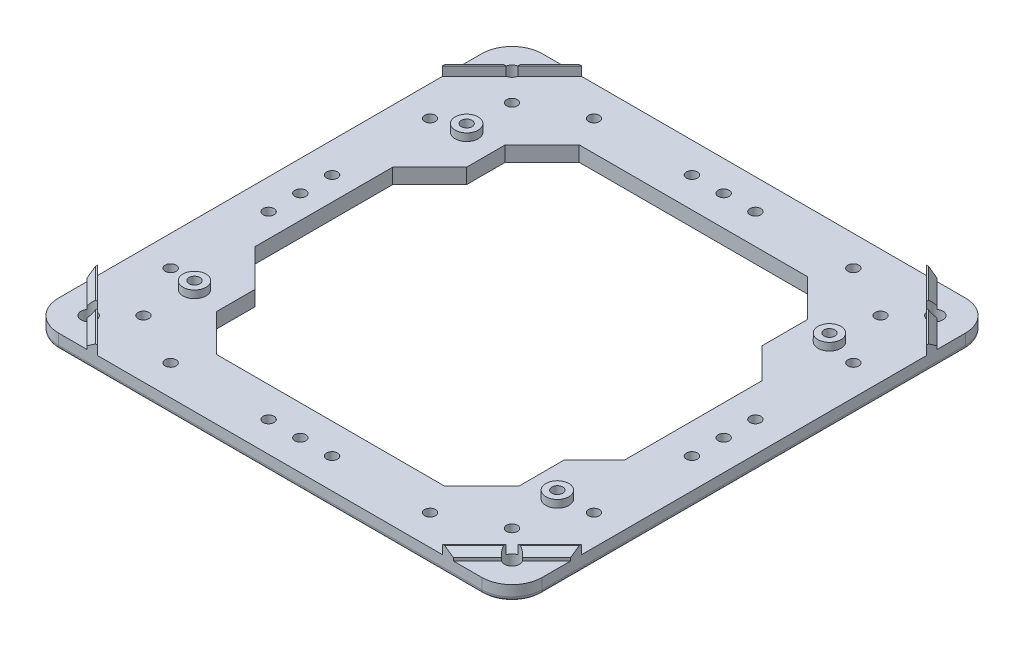
SolidWorks part; units mm, degrees
ref_plane "Front Plane" through (0, 0, 0) normal (0, 0, 1) x (1, 0, 0)
ref_plane "Top Plane" through (0, 0, 0) normal (0, 1, 0) x (1, 0, 0)
ref_plane "Right Plane" through (0, 0, 0) normal (1, 0, 0) x (0, 0, -1)
sketch "Sketch1" plane through (0, 0, 0) normal (0, 1, 0) x (1, 0, 0)
  line L1 (0, 0) -> (203.2, 0)
  line L2 (0, 0) -> (0, 203.2)
  line L3 (0, 203.2) -> (203.2, 203.2)
  line L4 (203.2, 0) -> (203.2, 203.2)
  dimension "D1" = 203.2
  dimension "D2" = 203.2
extrude "Boss-Extrude1" add sketch "Sketch1" along normal blind 6.35
fillet "Fillet1" radius 12.7 4 edges at (0, 3.175, -203.2) (0, 3.175, 0) (203.2, 3.175, 0) (203.2, 3.175, -203.2)
sketch "Sketch2" plane through (0, 0, 0) normal (0, -1, 0) x (1, 0, 0)
  circle A0 centre (12.7, -12.7) radius 3.175
  circle A1 centre (190.5, -12.7) radius 3.175
  circle A2 centre (190.5, -190.5) radius 3.175
  circle A3 centre (12.7, -190.5) radius 3.175
  arc A4 (190.5, -203.2) -> (203.2, -190.5) centre (190.5, -190.5) ccw construction
  arc A5 (12.7, 0) -> (0, -12.7) centre (12.7, -12.7) ccw construction
  arc A6 (12.7, 0) -> (0, -12.7) centre (12.7, -12.7) ccw construction
  dimension "D1" = 6.35
  dimension "D2" = 9.525
extrude "Cut-Extrude1" cut sketch "Sketch2" against normal through all
fillet "Fillet2" radius 1.905 8 edges at (3.7197, 0, -3.7197) (101.6, 0, 0) (199.4803, 0, -3.7197) (203.2, 0, -101.6) (199.4803, 0, -199.4803) (101.6, 0, -203.2) (3.7197, 0, -199.4803) (0, 0, -101.6)
sketch "Sketch3" plane through (0, 6.35, 0) normal (0, 1, 0) x (1, 0, 0)
  line L0 (3.7197, 3.7197) -> (24.1978, 24.1978) construction
  line L1 (24.1978, 24.1978) -> (0, 24.1978) construction
  line L2 (0, 190.5) -> (0, 12.7) construction
  line L3 (24.1978, 24.1978) -> (24.1978, 0) construction
  line L4 (12.7, 0) -> (190.5, 0) construction
  line L5 (3.7197, 199.4803) -> (24.1978, 179.0022) construction
  line L6 (0, 179.0022) -> (24.1978, 179.0022) construction
  line L7 (24.1978, 179.0022) -> (24.1978, 203.2) construction
  line L8 (190.5, 203.2) -> (12.7, 203.2) construction
  line L9 (199.4803, 3.7197) -> (179.0022, 24.1978) construction
  line L10 (179.0022, 24.1978) -> (179.0022, 0) construction
  line L12 (179.0022, 24.1978) -> (203.2, 24.1978) construction
  line L13 (203.2, 12.7) -> (203.2, 190.5) construction
  line L14 (199.4803, 199.4803) -> (179.0022, 179.0022) construction
  line L15 (179.0022, 179.0022) -> (203.2, 179.0022) construction
  line L16 (179.0022, 179.0022) -> (179.0022, 203.2) construction
  arc A0 (0, 12.7) -> (12.7, 0) centre (12.7, 12.7) ccw construction
  circle A1 centre (24.1978, 24.1978) radius 2.286
  arc A2 (190.5, 0) -> (203.2, 12.7) centre (190.5, 12.7) ccw construction
  arc A3 (203.2, 190.5) -> (190.5, 203.2) centre (190.5, 190.5) ccw construction
  arc A10 (12.7, 203.2) -> (0, 190.5) centre (12.7, 190.5) ccw construction
  circle A13 centre (179.0022, 179.0022) radius 2.286
  circle A14 centre (179.0022, 24.1978) radius 2.286
  circle A15 centre (24.1978, 179.0022) radius 2.286
  point P20 (101.6, 101.6)
  dimension "D2" = 4.572
  dimension "D1" = 28.9603
extrude "Cut-Extrude2" cut sketch "Sketch3" against normal through all
sketch "Sketch4" plane through (0, 6.35, 0) normal (0, 1, 0) x (1, 0, 0)
  line L0 (0, 190.5) -> (0, 12.7) construction
  line L1 (203.2, 12.7) -> (203.2, 190.5) construction
  line L2 (12.7, 0) -> (190.5, 0) construction
  line L3 (3.7197, 3.7197) -> (199.4803, 199.4803) construction
  circle A0 centre (47.117, 12.7) radius 2.286
  circle A1 centre (156.083, 12.7) radius 2.286
  arc A2 (0, 12.7) -> (12.7, 0) centre (12.7, 12.7) ccw construction
  arc A3 (203.2, 190.5) -> (190.5, 203.2) centre (190.5, 190.5) ccw construction
  circle A4 centre (12.7, 156.083) radius 2.286
  circle A5 centre (12.7, 47.117) radius 2.286
  circle A6 centre (156.083, 190.5) radius 2.286
  circle A7 centre (47.117, 190.5) radius 2.286
  circle A8 centre (190.5, 47.117) radius 2.286
  circle A9 centre (190.5, 156.083) radius 2.286
  circle A10 centre (101.6, 12.7) radius 2.286
  circle A11 centre (12.7, 101.6) radius 2.286
  circle A12 centre (101.6, 190.5) radius 2.286
  circle A13 centre (190.5, 101.6) radius 2.286
  point P18 (101.6, 101.6)
  dimension "D4" = 4.572
  dimension "D1" = 47.117
  dimension "D2" = 47.117
  dimension "D3" = 12.7
  dimension "D6" = 104.267
  dimension "D7" = 34.417
  dimension "D8" = 54.483
  dimension "D5" = 4
extrude "Cut-Extrude3" cut sketch "Sketch4" against normal through all
sketch "Sketch5" plane through (0, 6.35, 0) normal (0, 1, 0) x (1, 0, 0)
  line L0 (0, 190.5) -> (0, 12.7) construction
  line L1 (203.2, 12.7) -> (203.2, 190.5) construction
  line L2 (12.7, 0) -> (190.5, 0) construction
  line L3 (190.5, 203.2) -> (12.7, 203.2) construction
  circle A0 centre (25.4, 158.75) radius 2.286
  circle A1 centre (177.8, 158.75) radius 2.286
  circle A2 centre (177.8, 44.45) radius 2.286
  circle A3 centre (25.4, 44.45) radius 2.286
  circle A4 centre (25.4, 158.75) radius 4.826
  circle A5 centre (177.8, 158.75) radius 4.826
  circle A6 centre (177.8, 44.45) radius 4.826
  circle A7 centre (25.4, 44.45) radius 4.826
  dimension "D1" = 2.54
  dimension "D2" = 4.572
  dimension "D3" = 25.4
  dimension "D4" = 25.4
  dimension "D5" = 44.45
  dimension "D6" = 44.45
extrude "Boss-Extrude2" add sketch "Sketch5" along normal blind 3.175
sketch "Sketch6" plane through (0, 6.35, 0) normal (0, 1, 0) x (1, 0, 0)
  line L0 (203.2, 29.1287) -> (189.8864, 15.8151)
  line L1 (203.2, 12.7) -> (203.2, 190.5) construction
  line L2 (12.7, 0) -> (190.5, 0) construction
  line L3 (203.2, 29.1287) -> (203.2, 24.6386)
  line L4 (203.2, 24.6386) -> (193.0933, 14.5318)
  line L5 (178.5614, 0) -> (174.0713, 0)
  line L6 (187.3849, 13.3136) -> (174.0713, 0)
  line L7 (188.6682, 10.1067) -> (178.5614, 0)
  line L8 (3.7197, 3.7197) -> (199.4803, 199.4803) construction
  line L9 (13.3136, 15.8151) -> (0, 29.1287)
  line L10 (0, 24.6386) -> (0, 29.1287)
  line L11 (10.1067, 14.5318) -> (0, 24.6386)
  line L12 (24.6386, 0) -> (14.5318, 10.1067)
  line L13 (29.1287, 0) -> (15.8151, 13.3136)
  line L14 (29.1287, 0) -> (24.6386, 0)
  line L15 (15.8151, 189.8864) -> (29.1287, 203.2)
  line L16 (24.6386, 203.2) -> (29.1287, 203.2)
  line L17 (14.5318, 193.0933) -> (24.6386, 203.2)
  line L18 (0, 178.5614) -> (10.1067, 188.6682)
  line L19 (0, 174.0713) -> (13.3136, 187.3849)
  line L20 (0, 174.0713) -> (0, 178.5614)
  line L21 (189.8864, 187.3849) -> (203.2, 174.0713)
  line L22 (203.2, 178.5614) -> (203.2, 174.0713)
  line L23 (193.0933, 188.6682) -> (203.2, 178.5614)
  line L24 (178.5614, 203.2) -> (188.6682, 193.0933)
  line L25 (174.0713, 203.2) -> (187.3849, 189.8864)
  line L26 (174.0713, 203.2) -> (178.5614, 203.2)
  arc A0 (187.3849, 13.3136) -> (188.6682, 10.1067) centre (190.5, 12.7) ccw
  arc A1 (193.0933, 14.5318) -> (189.8864, 15.8151) centre (190.5, 12.7) ccw
  arc A2 (0, 12.7) -> (12.7, 0) centre (12.7, 12.7) ccw construction
  arc A3 (203.2, 190.5) -> (190.5, 203.2) centre (190.5, 190.5) ccw construction
  arc A4 (13.3136, 15.8151) -> (10.1067, 14.5318) centre (12.7, 12.7) ccw
  arc A5 (14.5318, 10.1067) -> (15.8151, 13.3136) centre (12.7, 12.7) ccw
  arc A6 (15.8151, 189.8864) -> (14.5318, 193.0933) centre (12.7, 190.5) ccw
  arc A7 (10.1067, 188.6682) -> (13.3136, 187.3849) centre (12.7, 190.5) ccw
  arc A8 (189.8864, 187.3849) -> (193.0933, 188.6682) centre (190.5, 190.5) ccw
  arc A9 (188.6682, 193.0933) -> (187.3849, 189.8864) centre (190.5, 190.5) ccw
  point P22 (101.6, 101.6)
  dimension "D4" = 6.35
  dimension "D1" = 29.1287
  dimension "D2" = 29.1287
  dimension "D3" = 3.175
  dimension "D6" = 177.8
  dimension "D5" = 4
extrude "Boss-Extrude3" add sketch "Sketch6" along normal blind 3.81
chamfer "Chamfer1" distance 2.54 angle 45 8 edges at (198.1466, 10.16, -19.5852) (183.6148, 10.16, -5.0534) (198.1466, 10.16, -183.6148) (183.6148, 10.16, -198.1466) (19.5852, 10.16, -198.1466) (5.0534, 10.16, -183.6148) (19.5852, 10.16, -5.0534) (5.0534, 10.16, -19.5852)
sketch "Sketch7" plane through (0, 6.35, 0) normal (0, 1, 0) x (1, 0, 0)
  line L0 (38.1, 57.15) -> (38.1, 25.4)
  line L1 (38.1, 177.8) -> (165.1, 177.8)
  line L2 (38.1, 177.8) -> (38.1, 146.05)
  line L3 (38.1, 25.4) -> (165.1, 25.4)
  line L4 (165.1, 177.8) -> (165.1, 146.05)
  line L5 (38.1, 57.15) -> (22.5685, 57.15)
  line L7 (38.1, 146.05) -> (22.5685, 146.05)
  line L8 (22.5685, 57.15) -> (22.5685, 146.05)
  line L9 (165.1, 57.15) -> (177.8, 57.15)
  line L11 (165.1, 146.05) -> (177.8, 146.05)
  line L12 (177.8, 57.15) -> (177.8, 146.05)
  line L13 (165.1, 57.15) -> (165.1, 25.4)
  circle A0 centre (47.117, 190.5) radius 2.286 construction
  circle A1 centre (101.6, 12.7) radius 2.286 construction
  circle A2 centre (177.8, 44.45) radius 4.826 construction
  circle A3 centre (25.4, 44.45) radius 2.286 construction
  circle A4 centre (190.5, 156.083) radius 2.286 construction
  circle A5 centre (177.8, 158.75) radius 4.826 construction
  circle A6 centre (25.4, 44.45) radius 4.826 construction
  dimension "D6" = 12.7
  dimension "D8" = 12.7
  dimension "D1" = 12.7
  dimension "D2" = 12.7
  dimension "D3" = 12.7
  dimension "D4" = 12.7
  dimension "D5" = 12.7
  dimension "D7" = 12.7
extrude "Cut-Extrude4" cut sketch "Sketch7" against normal through all
chamfer "Chamfer2" distance 15.5448 angle 45 8 edges at (22.5685, 3.175, -57.15) (38.1, 3.175, -25.4) (165.1, 3.175, -25.4) (177.8, 3.175, -57.15) (177.8, 3.175, -146.05) (165.1, 3.175, -177.8) (38.1, 3.175, -177.8) (22.5685, 3.175, -146.05)
sketch "Sketch8" plane through (0, 6.35, 0) normal (0, 1, 0) x (1, 0, 0)
  line L0 (88.265, 12.7) -> (114.935, 12.7) construction
  line L1 (3.7197, 3.7197) -> (199.4803, 199.4803) construction
  circle A0 centre (88.265, 12.7) radius 2.286
  circle A1 centre (114.935, 12.7) radius 2.286
  circle A2 centre (101.6, 12.7) radius 2.286 construction
  circle A3 centre (101.6, 12.7) radius 2.286
  arc A4 (0, 12.7) -> (12.7, 0) centre (12.7, 12.7) ccw construction
  arc A5 (203.2, 190.5) -> (190.5, 203.2) centre (190.5, 190.5) ccw construction
  circle A6 centre (12.7, 114.935) radius 2.286
  circle A7 centre (12.7, 88.265) radius 2.286
  circle A8 centre (114.935, 190.5) radius 2.286
  circle A9 centre (88.265, 190.5) radius 2.286
  circle A10 centre (190.5, 88.265) radius 2.286
  circle A11 centre (190.5, 114.935) radius 2.286
  point P4 (101.6, 12.7)
  point P16 (101.6, 101.6)
  dimension "D1" = 4.572
  dimension "D2" = 26.67
  dimension "D4" = 75.565
  dimension "D5" = 89.8946
  dimension "D3" = 4
extrude "Cut-Extrude5" cut sketch "Sketch8" against normal through all
